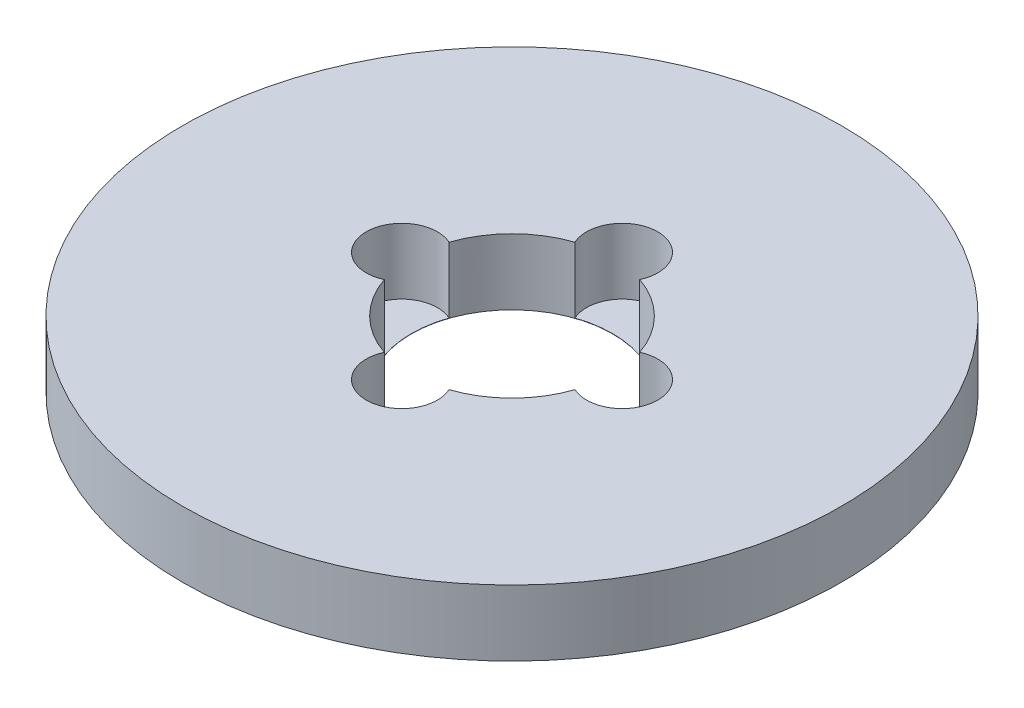
SolidWorks part; units mm, degrees
ref_plane "Front Plane" through (0, 0, 0) normal (0, 0, 1) x (1, 0, 0)
ref_plane "Top Plane" through (0, 0, 0) normal (0, 1, 0) x (1, 0, 0)
ref_plane "Right Plane" through (0, 0, 0) normal (1, 0, 0) x (0, 0, -1)
sketch "Sketch1" plane through (0, 0, 0) normal (0, 1, 0) x (1, 0, 0)
  circle A0 centre (0, 0) radius 90
  dimension "FLANGE_OD" = 180
extrude "Boss-Extrude1" add sketch "Sketch1" along normal blind 18
sketch "Sketch2" plane through (0, 0, 0) normal (0, 1, 0) x (1, 0, 0)
  circle A0 centre (0, 0) radius 27.5
  dimension "BORE_D" = 55
extrude "Cut-Extrude1" cut sketch "Sketch2" along normal through all
sketch "Sketch3" plane through (0, 18, 0) normal (0, 1, 0) x (1, 0, 0)
  circle A0 centre (0, 0) radius 30.0894 construction
  circle A1 centre (-30.0894, 0) radius 9.726
  dimension "BOLT_D" = 19.4521
  dimension "BOLT_PCD" = 60.1787
extrude "Cut-Extrude2" cut sketch "Sketch3" against normal blind 17.934
pattern_circular "CirPattern1" count 4 over 360 about axis through (0, 0, 0) along (0, 1, 0) of "Cut-Extrude2"
